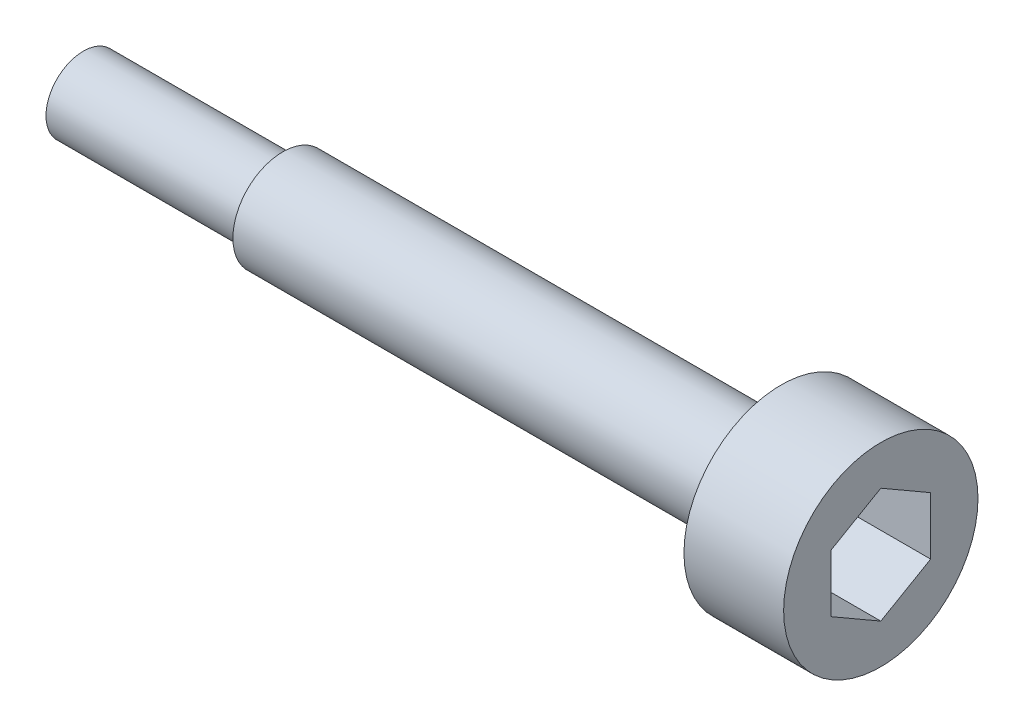
SolidWorks part; units mm, degrees
ref_plane "前视基准面" through (0, 0, 0) normal (0, 0, 1) x (1, 0, 0)
ref_plane "上视基准面" through (0, 0, 0) normal (0, 1, 0) x (1, 0, 0)
ref_plane "右视基准面" through (0, 0, 0) normal (1, 0, 0) x (0, 0, -1)
sketch "草图2" plane through (0, 0, 0) normal (0, 0, 1) x (1, 0, 0)
  line L0 (0, 0) -> (30.0827, 0) construction
  line L1 (0, 0) -> (0, 1.5)
  line L2 (0, 1.5) -> (8, 1.5)
  line L3 (8, 1.5) -> (8, 2)
  line L4 (8, 2) -> (28, 2)
  line L5 (28, 2) -> (28, 3.9)
  line L6 (28, 3.9) -> (32, 3.9)
  line L7 (32, 3.9) -> (32, 0)
  line L8 (32, 0) -> (0, 0)
  dimension "D1" = 3
  dimension "D2" = 4
  dimension "D3" = 7.8
  dimension "D4" = 4
  dimension "D5" = 20
  dimension "D6" = 8
revolve "旋转1" add sketch "草图2" angle 360 about L0
cosmetic thread "装饰螺纹线1" parameters "D2"=2.459
sketch "草图3" plane through (32, 0, 0) normal (1, 0, 0) x (0, 0, -1)
  line L1 (0, 2.3094) -> (-2, 1.1547)
  line L2 (-2, 1.1547) -> (-2, -1.1547)
  line L3 (-2, -1.1547) -> (0, -2.3094)
  line L4 (0, -2.3094) -> (2, -1.1547)
  line L5 (2, -1.1547) -> (2, 1.1547)
  line L6 (2, 1.1547) -> (0, 2.3094)
  circle A0 centre (0, 0) radius 2 construction
  dimension "D1" = 4
extrude "切除-拉伸1" cut sketch "草图3" against normal blind 3
